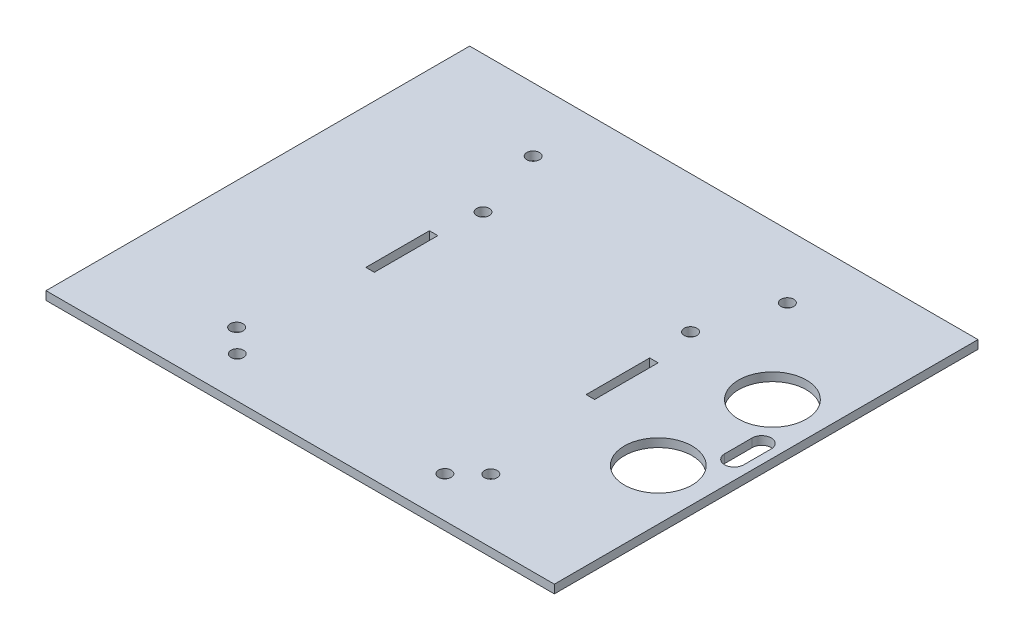
SolidWorks part; units mm, degrees
ref_plane "前基準面" through (0, 0, 0) normal (0, 0, 1) x (1, 0, 0)
ref_plane "上基準面" through (0, 0, 0) normal (0, 1, 0) x (1, 0, 0)
ref_plane "右基準面" through (0, 0, 0) normal (1, 0, 0) x (0, 0, -1)
sketch "草圖1" plane through (0, 0, 0) normal (0, 1, 0) x (1, 0, 0)
  line L0 (27, 0) -> (25, 0) construction
  line L1 (-60, -50) -> (60, -50)
  line L2 (-60, -50) -> (-60, 50)
  line L3 (-60, 50) -> (60, 50)
  line L4 (60, -50) -> (60, 50)
  line L5 (-69.2627, 0) -> (69.2627, 0) construction
  line L6 (0, 50) -> (0, -50) construction
  line L7 (-28, -42.5) -> (28, -42.5) construction
  line L8 (-28, -42.5) -> (-28, 42.5) construction
  line L9 (-28, 42.5) -> (28, 42.5) construction
  line L10 (28, -42.5) -> (28, 42.5) construction
  line L11 (0, 42.5) -> (0, -42.5) construction
  line L12 (-28, 0) -> (28, 0) construction
  line L13 (-27, -7.5) -> (-25, -7.5)
  line L14 (-27, -7.5) -> (-27, 7.5)
  line L15 (-27, 7.5) -> (-25, 7.5)
  line L16 (-25, -7.5) -> (-25, 7.5)
  line L17 (-26, 7.5) -> (-26, -7.5) construction
  line L18 (-27, 0) -> (-25, 0) construction
  line L19 (26, 7.5) -> (26, -7.5) construction
  line L20 (25, -7.5) -> (25, 7.5)
  line L21 (27, 7.5) -> (25, 7.5)
  line L22 (27, -7.5) -> (27, 7.5)
  line L23 (27, -7.5) -> (25, -7.5)
  circle A0 centre (-30, 35) radius 1.5
  circle A1 centre (30, 35) radius 1.5
  circle A2 centre (30, -35) radius 1.5
  circle A3 centre (-30, -35) radius 1.5
  circle A4 centre (24.5, 17.65) radius 1.5
  circle A5 centre (24.5, -40.35) radius 1.5
  circle A6 centre (-24.5, 17.65) radius 1.5
  circle A7 centre (-24.5, -40.35) radius 1.5
  point P0 (0, 0)
  point P15 (0, 0)
  point P26 (-26, 0)
  point P42 (26, 0)
  point P43 (-29.2687, 0)
  point P44 (21.7313, -17.7404)
  point P45 (24.3657, -17.7404)
  point P46 (28.1022, -16.9032)
  point P47 (27.4641, -16.0525)
  point P48 (27, -17.7404)
  point P49 (24.3657, -10.2404)
  point P50 (24.3657, -25.2404)
  point P51 (24.3657, -25.2404)
  point P52 (24.3657, -25.2404)
  point P53 (24.3657, -25.2404)
  point P54 (24.3657, -25.2404)
  point P55 (0, 0)
  point P56 (33.7709, 0)
  point P57 (0, 0)
  point P58 (30, 0)
  point P59 (0, 0)
  dimension "D1" = 3
  dimension "D6" = 24.85
  dimension "D7" = 3
  dimension "D2" = 70
  dimension "D3" = 60
  dimension "D4" = 85
  dimension "D5" = 56
  dimension "D8" = 49
  dimension "D9" = 58
  dimension "D10" = 100
  dimension "D11" = 120
  dimension "D12" = 50
  dimension "D13" = 15
  dimension "D14" = 2
extrude "填料-伸長1" add sketch "草圖1" along normal blind 2
sketch "草圖2" plane through (0, 2, 0) normal (0, 1, 0) x (1, 0, 0)
  line L0 (-98.9686, 0) -> (98.9686, 0) construction
  line L1 (55.7, -3.25) -> (55.7, 3.25) construction
  line L2 (53.45, -3.25) -> (53.45, 3.25)
  line L3 (57.95, -3.25) -> (57.95, 3.25)
  line L5 (58.35, 22.25) -> (37.65, 22.25) construction
  line L6 (58.35, 22.25) -> (58.35, -22.25) construction
  line L7 (58.35, -22.25) -> (37.65, -22.25) construction
  line L8 (37.65, 22.25) -> (37.65, -22.25) construction
  line L9 (48, -22.25) -> (48, 22.25) construction
  line L10 (58.35, 0) -> (37.65, 0) construction
  circle A0 centre (48, 13.48) radius 8
  circle A1 centre (48, -13.48) radius 8
  arc A2 (53.45, -3.25) -> (57.95, -3.25) centre (55.7, -3.25) ccw
  arc A3 (57.95, 3.25) -> (53.45, 3.25) centre (55.7, 3.25) ccw
  point P4 (0, 0)
  point P10 (55.7, 0)
  point P15 (48, 0)
  point P19 (55.8058, 0)
  point P20 (42.9639, 0)
  dimension "D2" = 16
  dimension "D1" = 26.96
  dimension "D3" = 20.7
  dimension "D4" = 0.4
  dimension "D5" = 6.5
  dimension "D6" = 4.5
  dimension "D7" = 44.5
  dimension "D8" = 48
extrude "除料-伸長1" cut sketch "草圖2" against normal through all
